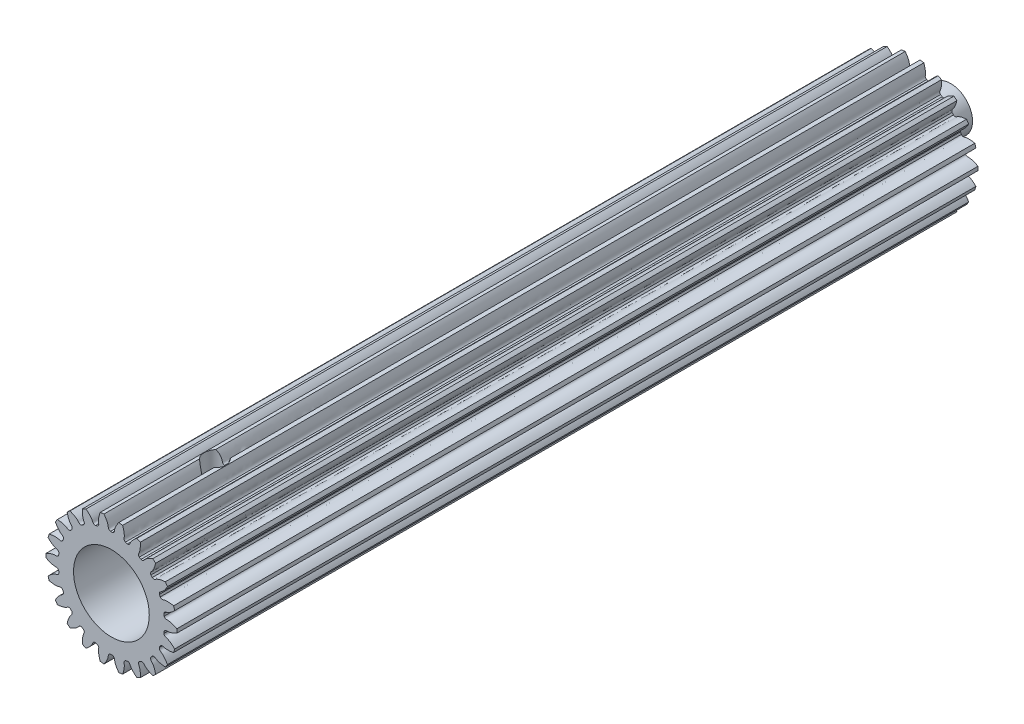
SolidWorks part; units mm, degrees
ref_plane "前视基准面" through (0, 0, 0) normal (0, 0, 1) x (1, 0, 0)
ref_plane "上视基准面" through (0, 0, 0) normal (0, 1, 0) x (1, 0, 0)
ref_plane "右视基准面" through (0, 0, 0) normal (1, 0, 0) x (0, 0, -1)
sketch "草图1" plane through (0, 0, 0) normal (0, 0, 1) x (1, 0, 0)
  circle A0 centre (0, 0) radius 12
extrude "凸台-拉伸1" add sketch "草图1" along normal blind 30
ref_axis "基准轴1" through (0, 0, -1.5) along (0, 0, 1)
sketch "草图2" plane through (0, 0, 0) normal (0, 0, 1) x (1, 0, 0)
  line L0 (0, 0) -> (0, 12) construction
  circle A0 centre (0, 0) radius 12 construction
  arc A1 (0.1857, 9.7482) -> (-0.1857, 9.7482) centre (0, 0) ccw
  arc A2 (3.0856, 13.5599) -> (-3.0856, 13.5599) centre (0, 0) ccw
  spline S0 degree 3 poles (0.1857, 9.7482) (0.5882, 9.8762) (0.5483, 10.1518) (0.5996, 10.4216) (0.606, 10.4519) (0.6139, 10.4862) (0.6235, 10.5243) (0.6349, 10.5661) (0.6484, 10.6117) (0.664, 10.661) (0.6819, 10.7139) (0.7023, 10.7703) (0.7253, 10.8301) (0.7511, 10.8933) (0.7797, 10.9597) (0.8114, 11.0293) (0.8462, 11.1021) (0.8843, 11.1778) (0.9259, 11.2563) (0.9711, 11.3377) (1.0199, 11.4217) (1.0726, 11.5082) (1.1292, 11.5972) (1.1899, 11.6884) (1.2547, 11.7818) (1.3238, 11.8773) (1.3973, 11.9746) (1.4753, 12.0737) (1.5579, 12.1744) (1.6452, 12.2766) (1.7372, 12.3802) (1.8341, 12.4849) (1.9359, 12.5906) (2.0428, 12.6972) (2.1547, 12.8044) (2.2718, 12.9123) (2.3942, 13.0205) (2.5218, 13.1289) (2.6548, 13.2373) (2.8415, 13.3834) (2.9864, 13.49) (3.0856, 13.5599) knots 0 0 0 0 0.157021 0.162531 0.168888 0.176093 0.184146 0.193046 0.202794 0.213389 0.224833 0.237123 0.250262 0.264248 0.279082 0.294763 0.311292 0.328669 0.346893 0.365965 0.385884 0.406652 0.428266 0.450729 0.474039 0.498197 0.523202 0.549055 0.575756 0.603304 0.6317 0.660944 0.691035 0.721974 0.75376 0.786395 0.819876 0.854206 0.889383 0.925408 1 1 1 1
  spline S1 degree 3 poles (-0.1857, 9.7482) (-0.5882, 9.8762) (-0.5483, 10.1518) (-0.5996, 10.4216) (-0.606, 10.4519) (-0.6139, 10.4862) (-0.6235, 10.5243) (-0.6349, 10.5661) (-0.6484, 10.6117) (-0.664, 10.661) (-0.6819, 10.7139) (-0.7023, 10.7703) (-0.7253, 10.8301) (-0.7511, 10.8933) (-0.7797, 10.9597) (-0.8114, 11.0293) (-0.8462, 11.1021) (-0.8843, 11.1778) (-0.9259, 11.2563) (-0.9711, 11.3377) (-1.0199, 11.4217) (-1.0726, 11.5082) (-1.1292, 11.5972) (-1.1899, 11.6884) (-1.2547, 11.7818) (-1.3238, 11.8773) (-1.3973, 11.9746) (-1.4753, 12.0737) (-1.5579, 12.1744) (-1.6452, 12.2766) (-1.7372, 12.3802) (-1.8341, 12.4849) (-1.9359, 12.5906) (-2.0428, 12.6972) (-2.1547, 12.8044) (-2.2718, 12.9123) (-2.3942, 13.0205) (-2.5218, 13.1289) (-2.6548, 13.2373) (-2.8415, 13.3834) (-2.9864, 13.49) (-3.0856, 13.5599) knots 0 0 0 0 0.157021 0.162531 0.168888 0.176093 0.184146 0.193046 0.202794 0.213389 0.224833 0.237123 0.250262 0.264248 0.279082 0.294763 0.311292 0.328669 0.346893 0.365965 0.385884 0.406652 0.428266 0.450729 0.474039 0.498197 0.523202 0.549055 0.575756 0.603304 0.6317 0.660944 0.691035 0.721974 0.75376 0.786395 0.819876 0.854206 0.889383 0.925408 1 1 1 1
extrude "切除-拉伸1" cut sketch "草图2" along normal through all
pattern_circular "阵列(圆周)1" count 22 every 16.364 about axis through (0, 0, -1.5) along (0, 0, 1) of "切除-拉伸1"
sketch "草图3" plane through (0, 0, 0) normal (0, 0, 1) x (1, 0, 0)
  circle A0 centre (0, 0) radius 11 construction
  dimension "Dn" = 22
sketch "草图4" plane through (0, 0, 0) normal (0, 0, -1) x (-1, 0, 0)
  arc A45 (2.9245, 9.3011) -> (2.5682, 9.4057) centre (0, 0) ccw
  arc A46 (2.0557, 11.8226) -> (1.3584, 11.9229) centre (0, 0) ccw
  arc A47 (0.1857, 9.7482) -> (-0.1857, 9.7482) centre (0, 0) ccw
  arc A48 (-1.3584, 11.9229) -> (-2.0557, 11.8226) centre (0, 0) ccw
  arc A49 (-2.5682, 9.4057) -> (-2.9245, 9.3011) centre (0, 0) ccw
  arc A50 (-4.6624, 11.0572) -> (-5.3032, 10.7646) centre (0, 0) ccw
  arc A51 (-5.1141, 8.3011) -> (-5.4265, 8.1004) centre (0, 0) ccw
  arc A52 (-7.5887, 9.2958) -> (-8.1211, 8.8344) centre (0, 0) ccw
  arc A53 (-7.2456, 6.5241) -> (-7.4888, 6.2434) centre (0, 0) ccw
  arc A54 (-9.9003, 6.7812) -> (-10.2811, 6.1886) centre (0, 0) ccw
  arc A55 (-8.7902, 4.2184) -> (-8.9444, 3.8807) centre (0, 0) ccw
  arc A56 (-11.4097, 3.7173) -> (-11.6082, 3.0414) centre (0, 0) ccw
  arc A57 (-9.6226, 1.5711) -> (-9.6754, 1.2035) centre (0, 0) ccw
  arc A58 (-11.9948, 0.3522) -> (-11.9948, -0.3522) centre (0, 0) ccw
  arc A59 (-9.6754, -1.2035) -> (-9.6226, -1.5711) centre (0, 0) ccw
  arc A60 (-11.6082, -3.0414) -> (-11.4097, -3.7173) centre (0, 0) ccw
  arc A61 (-8.9444, -3.8807) -> (-8.7902, -4.2184) centre (0, 0) ccw
  arc A62 (-10.2811, -6.1886) -> (-9.9003, -6.7812) centre (0, 0) ccw
  arc A63 (-7.4888, -6.2434) -> (-7.2456, -6.5241) centre (0, 0) ccw
  arc A64 (-8.1211, -8.8344) -> (-7.5887, -9.2958) centre (0, 0) ccw
  arc A65 (-5.4265, -8.1004) -> (-5.1141, -8.3011) centre (0, 0) ccw
  arc A66 (-5.3032, -10.7646) -> (-4.6624, -11.0572) centre (0, 0) ccw
  arc A67 (-2.9245, -9.3011) -> (-2.5682, -9.4057) centre (0, 0) ccw
  arc A68 (-2.0557, -11.8226) -> (-1.3584, -11.9229) centre (0, 0) ccw
  arc A69 (-0.1857, -9.7482) -> (0.1857, -9.7482) centre (0, 0) ccw
  arc A70 (1.3584, -11.9229) -> (2.0557, -11.8226) centre (0, 0) ccw
  arc A71 (2.5682, -9.4057) -> (2.9245, -9.3011) centre (0, 0) ccw
  arc A72 (4.6624, -11.0572) -> (5.3032, -10.7646) centre (0, 0) ccw
  arc A73 (5.1141, -8.3011) -> (5.4265, -8.1004) centre (0, 0) ccw
  arc A74 (7.5887, -9.2958) -> (8.1211, -8.8344) centre (0, 0) ccw
  arc A75 (7.2456, -6.5241) -> (7.4888, -6.2434) centre (0, 0) ccw
  arc A76 (9.9003, -6.7812) -> (10.2811, -6.1886) centre (0, 0) ccw
  arc A77 (8.7902, -4.2184) -> (8.9444, -3.8807) centre (0, 0) ccw
  arc A78 (11.4097, -3.7173) -> (11.6082, -3.0414) centre (0, 0) ccw
  arc A79 (9.6226, -1.5711) -> (9.6754, -1.2035) centre (0, 0) ccw
  arc A80 (11.9948, -0.3522) -> (11.9948, 0.3522) centre (0, 0) ccw
  arc A81 (9.6754, 1.2035) -> (9.6226, 1.5711) centre (0, 0) ccw
  arc A82 (11.6082, 3.0414) -> (11.4097, 3.7173) centre (0, 0) ccw
  arc A83 (8.9444, 3.8807) -> (8.7902, 4.2184) centre (0, 0) ccw
  arc A84 (10.2811, 6.1886) -> (9.9003, 6.7812) centre (0, 0) ccw
  arc A85 (7.4888, 6.2434) -> (7.2456, 6.5241) centre (0, 0) ccw
  arc A86 (8.1211, 8.8344) -> (7.5887, 9.2958) centre (0, 0) ccw
  arc A87 (5.4265, 8.1004) -> (5.1141, 8.3011) centre (0, 0) ccw
  arc A88 (5.3032, 10.7646) -> (4.6624, 11.0572) centre (0, 0) ccw
  arc A89 (2.9245, 9.3011) -> (2.5682, 9.4057) centre (0, 0) ccw
  arc A90 (2.0557, 11.8226) -> (1.3584, 11.9229) centre (0, 0) ccw
  arc A91 (0.1857, 9.7482) -> (-0.1857, 9.7482) centre (0, 0) ccw
  arc A92 (-1.3584, 11.9229) -> (-2.0557, 11.8226) centre (0, 0) ccw
  arc A93 (-2.5682, 9.4057) -> (-2.9245, 9.3011) centre (0, 0) ccw
  arc A94 (-4.6624, 11.0572) -> (-5.3032, 10.7646) centre (0, 0) ccw
  arc A95 (-5.1141, 8.3011) -> (-5.4265, 8.1004) centre (0, 0) ccw
  arc A96 (-7.5887, 9.2958) -> (-8.1211, 8.8344) centre (0, 0) ccw
  arc A97 (-7.2456, 6.5241) -> (-7.4888, 6.2434) centre (0, 0) ccw
  arc A98 (-9.9003, 6.7812) -> (-10.2811, 6.1886) centre (0, 0) ccw
  arc A99 (-8.7902, 4.2184) -> (-8.9444, 3.8807) centre (0, 0) ccw
  arc A100 (-11.4097, 3.7173) -> (-11.6082, 3.0414) centre (0, 0) ccw
  arc A101 (-9.6226, 1.5711) -> (-9.6754, 1.2035) centre (0, 0) ccw
  arc A102 (-11.9948, 0.3522) -> (-11.9948, -0.3522) centre (0, 0) ccw
  arc A103 (-9.6754, -1.2035) -> (-9.6226, -1.5711) centre (0, 0) ccw
  arc A104 (-11.6082, -3.0414) -> (-11.4097, -3.7173) centre (0, 0) ccw
  arc A105 (-8.9444, -3.8807) -> (-8.7902, -4.2184) centre (0, 0) ccw
  arc A106 (-10.2811, -6.1886) -> (-9.9003, -6.7812) centre (0, 0) ccw
  arc A107 (-7.4888, -6.2434) -> (-7.2456, -6.5241) centre (0, 0) ccw
  arc A108 (-8.1211, -8.8344) -> (-7.5887, -9.2958) centre (0, 0) ccw
  arc A109 (-5.4265, -8.1004) -> (-5.1141, -8.3011) centre (0, 0) ccw
  arc A110 (-5.3032, -10.7646) -> (-4.6624, -11.0572) centre (0, 0) ccw
  arc A111 (-2.9245, -9.3011) -> (-2.5682, -9.4057) centre (0, 0) ccw
  arc A112 (-2.0557, -11.8226) -> (-1.3584, -11.9229) centre (0, 0) ccw
  arc A113 (-0.1857, -9.7482) -> (0.1857, -9.7482) centre (0, 0) ccw
  arc A114 (1.3584, -11.9229) -> (2.0557, -11.8226) centre (0, 0) ccw
  arc A115 (2.5682, -9.4057) -> (2.9245, -9.3011) centre (0, 0) ccw
  arc A116 (4.6624, -11.0572) -> (5.3032, -10.7646) centre (0, 0) ccw
  arc A117 (5.1141, -8.3011) -> (5.4265, -8.1004) centre (0, 0) ccw
  arc A118 (7.5887, -9.2958) -> (8.1211, -8.8344) centre (0, 0) ccw
  arc A119 (7.2456, -6.5241) -> (7.4888, -6.2434) centre (0, 0) ccw
  arc A120 (9.9003, -6.7812) -> (10.2811, -6.1886) centre (0, 0) ccw
  arc A121 (8.7902, -4.2184) -> (8.9444, -3.8807) centre (0, 0) ccw
  arc A122 (11.4097, -3.7173) -> (11.6082, -3.0414) centre (0, 0) ccw
  arc A123 (9.6226, -1.5711) -> (9.6754, -1.2035) centre (0, 0) ccw
  arc A124 (11.9948, -0.3522) -> (11.9948, 0.3522) centre (0, 0) ccw
  arc A125 (9.6754, 1.2035) -> (9.6226, 1.5711) centre (0, 0) ccw
  arc A126 (11.6082, 3.0414) -> (11.4097, 3.7173) centre (0, 0) ccw
  arc A127 (8.9444, 3.8807) -> (8.7902, 4.2184) centre (0, 0) ccw
  arc A128 (10.2811, 6.1886) -> (9.9003, 6.7812) centre (0, 0) ccw
  arc A129 (7.4888, 6.2434) -> (7.2456, 6.5241) centre (0, 0) ccw
  arc A130 (8.1211, 8.8344) -> (7.5887, 9.2958) centre (0, 0) ccw
  arc A131 (5.4265, 8.1004) -> (5.1141, 8.3011) centre (0, 0) ccw
  arc A132 (5.3032, 10.7646) -> (4.6624, 11.0572) centre (0, 0) ccw
  spline S44 degree 3 poles (-3755.952, 1373.0737) (154.5775, -91.5166) (23.7539, 27.4151) (4.2738, 10.7434) (4.1283, 10.6084) (3.9999, 10.4794) (3.888, 10.3576) (3.7917, 10.2441) (3.7102, 10.1398) (3.6518, 10.0587) (3.6037, 9.9872) (3.5713, 9.9359) (3.5381, 9.8795) (3.5167, 9.8409) (1.2241, 5.3639) (28.0313, -13.6031) (-3366.6388, 2164.2652) knots -15.132265 -15.132265 -15.132265 -15.132265 0.549271 0.593348 0.634035 0.671331 0.705237 0.735752 0.762877 0.786611 0.797206 0.815854 0.823907 0.837469 0.842979 3.91725 3.91725 3.91725 3.91725 only from (4.6624, 11.0572) to (2.9245, 9.3011)
  spline S45 degree 3 poles (4001.8856, 0.5536) (-30.9337, 3.7113) (1.8702, 5.1744) (2.3619, 10.18) (2.3658, 10.2385) (2.3681, 10.3211) (2.3668, 10.4204) (2.3608, 10.536) (2.3486, 10.6678) (2.329, 10.8154) (2.3007, 10.9784) (2.2624, 11.1562) (2.213, 11.3485) (2.1511, 11.5544) (-6.7232, 37.3225) (-188.8794, -0.555) (3905.063, -861.7664) knots -2.917148 -2.917148 -2.917148 -2.917148 0.157021 0.162531 0.176093 0.193046 0.213389 0.237123 0.264248 0.294763 0.328669 0.365965 0.406652 0.450729 0.498197 17.164861 17.164861 17.164861 17.164861 only from (2.5682, 9.4057) to (2.0557, 11.8226)
  spline S46 degree 3 poles (-3990.6492, 259.2806) (174.0992, -44.26) (15.0679, 32.9969) (1.0739, 11.5123) (0.9723, 11.3417) (0.8855, 11.1818) (0.8124, 11.0334) (0.752, 10.8973) (0.7032, 10.7743) (0.6701, 10.6801) (0.644, 10.5979) (0.6274, 10.5396) (0.6113, 10.4761) (0.6018, 10.4331) (-0.3367, 5.4915) (30.7283, -5.1547) (-3840.0103, 1128.1054) knots -15.132265 -15.132265 -15.132265 -15.132265 0.549271 0.593348 0.634035 0.671331 0.705237 0.735752 0.762877 0.786611 0.797206 0.815854 0.823907 0.837469 0.842979 3.91725 3.91725 3.91725 3.91725 only from (1.3584, 11.9229) to (0.1857, 9.7482)
  spline S47 degree 3 poles (3839.6251, 1127.9927) (-30.7262, -5.154) (0.3366, 5.4917) (-0.6018, 10.4331) (-0.6145, 10.4903) (-0.6356, 10.5702) (-0.6648, 10.6651) (-0.7032, 10.7743) (-0.752, 10.8973) (-0.8124, 11.0334) (-0.8855, 11.1818) (-0.9723, 11.3417) (-1.0739, 11.5123) (-1.1913, 11.6924) (-16.9659, 33.9165) (-181.0721, -53.746) (3989.6681, 273.3246) knots -2.917148 -2.917148 -2.917148 -2.917148 0.157021 0.162531 0.176093 0.193046 0.213389 0.237123 0.264248 0.294763 0.328669 0.365965 0.406652 0.450729 0.498197 17.164861 17.164861 17.164861 17.164861 only from (-0.1857, 9.7482) to (-1.3584, 11.9229)
  spline S48 degree 3 poles (-3902.0476, -875.5179) (179.5164, 6.5822) (5.1613, 35.9054) (-2.213, 11.3485) (-2.2624, 11.1562) (-2.3007, 10.9784) (-2.329, 10.8154) (-2.3486, 10.6678) (-2.3608, 10.536) (-2.366, 10.4362) (-2.3678, 10.3501) (-2.3674, 10.2894) (-2.3649, 10.224) (-2.3619, 10.18) (-1.8702, 5.1742) (30.9358, 3.7112) (-4002.2869, 0.5533) knots -15.132265 -15.132265 -15.132265 -15.132265 0.549271 0.593348 0.634035 0.671331 0.705237 0.735752 0.762877 0.786611 0.797206 0.815854 0.823907 0.837469 0.842979 3.91725 3.91725 3.91725 3.91725 only from (-2.0557, 11.8226) to (-2.5682, 9.4057)
  spline S49 degree 3 poles (3366.3011, 2164.0485) (-28.0295, -13.6018) (-1.2242, 5.3641) (-3.5167, 9.8409) (-3.5451, 9.8922) (-3.5879, 9.963) (-3.6426, 10.0458) (-3.7102, 10.1398) (-3.7917, 10.2441) (-3.888, 10.3576) (-3.9999, 10.4794) (-4.1283, 10.6084) (-4.2738, 10.7434) (-4.4372, 10.8832) (-25.834, 27.7628) (-158.5954, -102.5828) (3751.0541, 1386.2724) knots -2.917148 -2.917148 -2.917148 -2.917148 0.157021 0.162531 0.176093 0.193046 0.213389 0.237123 0.264248 0.294763 0.328669 0.365965 0.406652 0.450729 0.498197 17.164861 17.164861 17.164861 17.164861 only from (-2.9245, 9.3011) to (-4.6624, 11.0572)
  spline S50 degree 3 poles (-3497.3254, -1939.3871) (170.3903, 56.8912) (-5.1635, 35.9051) (-5.3206, 10.2653) (-5.3138, 10.0669) (-5.3004, 9.8855) (-5.2817, 9.7211) (-5.2589, 9.574) (-5.2335, 9.4441) (-5.2104, 9.3469) (-5.1879, 9.2637) (-5.1704, 9.2057) (-5.1495, 9.1436) (-5.1343, 9.1022) (-3.2522, 4.4377) (28.6371, 12.2765) (-3840.322, -1127.0436) knots -15.132265 -15.132265 -15.132265 -15.132265 0.549271 0.593348 0.634035 0.671331 0.705237 0.735752 0.762877 0.786611 0.797206 0.815854 0.823907 0.837469 0.842979 3.91725 3.91725 3.91725 3.91725 only from (-5.3032, 10.7646) to (-5.1141, 8.3011)
  spline S51 degree 3 poles (2620.2593, 3024.7859) (-23.0621, -20.9477) (-2.6858, 4.8019) (-6.1468, 8.4515) (-6.1884, 8.4928) (-6.2494, 8.5486) (-6.3253, 8.6126) (-6.4166, 8.6838) (-6.5242, 8.7609) (-6.6486, 8.8427) (-6.7903, 8.928) (-6.9498, 9.0156) (-7.1274, 9.1041) (-7.3236, 9.1923) (-32.6092, 19.3599) (-123.2703, -143.109) (3208.552, 2386.9127) knots -2.917148 -2.917148 -2.917148 -2.917148 0.157021 0.162531 0.176093 0.193046 0.213389 0.237123 0.264248 0.294763 0.328669 0.365965 0.406652 0.450729 0.498197 17.164861 17.164861 17.164861 17.164861 only from (-5.4265, 8.1004) to (-7.5887, 9.2958)
  spline S52 degree 3 poles (-2809.2707, -2846.1387) (147.4602, 102.5913) (-15.07, 32.9959) (-7.9971, 8.3505) (-7.9348, 8.1621) (-7.8708, 7.9917) (-7.8065, 7.8393) (-7.7432, 7.7046) (-7.6822, 7.5871) (-7.6327, 7.5003) (-7.5876, 7.4269) (-7.5545, 7.3761) (-7.517, 7.3224) (-7.4907, 7.287) (-4.3707, 3.3417) (24.0184, 19.8472) (-3367.2371, -2163.3342) knots -15.132265 -15.132265 -15.132265 -15.132265 0.549271 0.593348 0.634035 0.671331 0.705237 0.735752 0.762877 0.786611 0.797206 0.815854 0.823907 0.837469 0.842979 3.91725 3.91725 3.91725 3.91725 only from (-8.1211, 8.8344) to (-7.2456, 6.5241)
  spline S53 degree 3 poles (1661.9397, 3640.4732) (-16.2262, -26.5965) (-3.9299, 3.8507) (-8.2789, 6.3774) (-8.3304, 6.4053) (-8.4047, 6.4416) (-8.4955, 6.4817) (-8.6032, 6.5243) (-8.7281, 6.5679) (-8.8705, 6.6114) (-9.0305, 6.6533) (-9.2082, 6.6924) (-9.4036, 6.7273) (-9.6167, 6.7566) (-36.7427, 9.3886) (-77.9585, -172.0413) (2406.1121, 3194.1795) knots -2.917148 -2.917148 -2.917148 -2.917148 0.157021 0.162531 0.176093 0.193046 0.213389 0.237123 0.264248 0.294763 0.328669 0.365965 0.406652 0.450729 0.498197 17.164861 17.164861 17.164861 17.164861 only from (-7.4888, 6.2434) to (-9.9003, 6.7812)
  spline S54 degree 3 poles (-1893.6255, -3522.3131) (112.5837, 139.9799) (-23.7556, 27.4137) (-10.0258, 5.7592) (-9.9129, 5.596) (-9.8035, 5.4506) (-9.6989, 5.3224) (-9.6002, 5.211) (-9.5086, 5.1155) (-9.4366, 5.0462) (-9.3727, 4.9884) (-9.3266, 4.949) (-9.2755, 4.908) (-9.2403, 4.8814) (-5.1351, 1.975) (17.4539, 25.8101) (-2621.3587, -3024.3643) knots -15.132265 -15.132265 -15.132265 -15.132265 0.549271 0.593348 0.634035 0.671331 0.705237 0.735752 0.762877 0.786611 0.797206 0.815854 0.823907 0.837469 0.842979 3.91725 3.91725 3.91725 3.91725 only from (-10.2811, 6.1886) to (-8.7902, 4.2184)
  spline S55 degree 3 poles (568.9797, 3961.231) (-8.0759, -30.0906) (-4.8556, 2.5876) (-9.7402, 3.7867) (-9.7976, 3.7989) (-9.8791, 3.8128) (-9.9775, 3.8257) (-10.0928, 3.8362) (-10.225, 3.8429) (-10.3738, 3.8445) (-10.5392, 3.8396) (-10.7207, 3.8271) (-10.918, 3.8055) (-11.1307, 3.7736) (-37.8994, -1.3433) (-26.331, -187.0359) (1408.7433, 3742.6729) knots -2.917148 -2.917148 -2.917148 -2.917148 0.157021 0.162531 0.176093 0.193046 0.213389 0.237123 0.264248 0.294763 0.328669 0.365965 0.406652 0.450729 0.498197 17.164861 17.164861 17.164861 17.164861 only from (-8.9444, 3.8807) to (-11.4097, 3.7173)
  spline S56 degree 3 poles (-824.5701, -3913.1306) (68.5864, 166.0283) (-30.5166, 19.6105) (-11.2422, 2.7013) (-11.0879, 2.5765) (-10.942, 2.4678) (-10.8055, 2.3743) (-10.6794, 2.2952) (-10.5646, 2.2294) (-10.476, 2.1832) (-10.3984, 2.1457) (-10.3431, 2.1209) (-10.2825, 2.096) (-10.2412, 2.0804) (-5.4835, 0.4483) (9.4754, 29.6819) (-1663.1134, -3640.3784) knots -15.132265 -15.132265 -15.132265 -15.132265 0.549271 0.593348 0.634035 0.671331 0.705237 0.735752 0.762877 0.786611 0.797206 0.815854 0.823907 0.837469 0.842979 3.91725 3.91725 3.91725 3.91725 only from (-11.6082, 3.0414) to (-9.6226, 1.5711)
  spline S57 degree 3 poles (-570.0757, 3961.0734) (0.7288, -31.147) (-5.3879, 1.1148) (-10.4125, 0.8891) (-10.4709, 0.8847) (-10.5531, 0.8751) (-10.6512, 0.8598) (-10.7647, 0.8373) (-10.8934, 0.8065) (-11.0367, 0.7661) (-11.194, 0.7149) (-11.3647, 0.6517) (-11.5479, 0.5754) (-11.743, 0.4849) (-35.9858, -11.9664) (27.4296, -186.8779) (297.2464, 3987.9572) knots -2.917148 -2.917148 -2.917148 -2.917148 0.157021 0.162531 0.176093 0.193046 0.213389 0.237123 0.264248 0.294763 0.328669 0.365965 0.406652 0.450729 0.498197 17.164861 17.164861 17.164861 17.164861 only from (-9.6754, 1.2035) to (-11.9948, 0.3522)
  spline S58 degree 3 poles (311.2871, -3986.9296) (19.0326, 178.626) (-34.8054, 10.2186) (-11.5479, -0.5754) (-11.3647, -0.6517) (-11.194, -0.7149) (-11.0367, -0.7661) (-10.8934, -0.8065) (-10.7647, -0.8373) (-10.6667, -0.8567) (-10.5817, -0.8708) (-10.5216, -0.879) (-10.4565, -0.8858) (-10.4125, -0.8891) (-5.3877, -1.1148) (0.7292, 31.1491) (-570.1325, -3961.4706) knots -15.132265 -15.132265 -15.132265 -15.132265 0.549271 0.593348 0.634035 0.671331 0.705237 0.735752 0.762877 0.786611 0.797206 0.815854 0.823907 0.837469 0.842979 3.91725 3.91725 3.91725 3.91725 only from (-11.9948, -0.3522) to (-9.6754, -1.2035)
  spline S59 degree 3 poles (-1662.947, 3640.0132) (9.4744, -29.68) (-5.4837, -0.4483) (-10.2412, -2.0804) (-10.296, -2.1012) (-10.3722, -2.1335) (-10.4619, -2.1758) (-10.5646, -2.2294) (-10.6794, -2.2952) (-10.8055, -2.3743) (-10.942, -2.4678) (-11.0879, -2.5765) (-11.2422, -2.7014) (-11.4039, -2.8432) (-31.1568, -21.62) (78.9681, -171.5802) (-838.3315, 3910.1609) knots -2.917148 -2.917148 -2.917148 -2.917148 0.157021 0.162531 0.176093 0.193046 0.213389 0.237123 0.264248 0.294763 0.328669 0.365965 0.406652 0.450729 0.498197 17.164861 17.164861 17.164861 17.164861 only from (-9.6226, -1.5711) to (-11.6082, -3.0414)
  spline S60 degree 3 poles (1421.9256, -3737.7312) (-32.0631, 176.7525) (-36.2745, -0.0011) (-10.918, -3.8055) (-10.7207, -3.8271) (-10.5392, -3.8396) (-10.3738, -3.8445) (-10.225, -3.8429) (-10.0928, -3.8362) (-9.9933, -3.8272) (-9.9078, -3.8167) (-9.8478, -3.8076) (-9.7834, -3.7958) (-9.7402, -3.7867) (-4.8554, -2.5875) (-8.0761, 30.0928) (569.0371, -3961.6281) knots -15.132265 -15.132265 -15.132265 -15.132265 0.549271 0.593348 0.634035 0.671331 0.705237 0.735752 0.762877 0.786611 0.797206 0.815854 0.823907 0.837469 0.842979 3.91725 3.91725 3.91725 3.91725 only from (-11.4097, -3.7173) to (-8.9444, -3.8807)
  spline S61 degree 3 poles (-2621.0962, 3024.0608) (17.4524, -25.8085) (-5.1353, -1.9751) (-9.2403, -4.8814) (-9.287, -4.9168) (-9.351, -4.9692) (-9.4251, -5.0352) (-9.5086, -5.1155) (-9.6002, -5.211) (-9.6989, -5.3224) (-9.8035, -5.4506) (-9.9129, -5.596) (-10.0258, -5.7592) (-10.1409, -5.9408) (-23.8037, -29.5221) (124.1091, -142.3821) (-1905.9928, 3515.5866) knots -2.917148 -2.917148 -2.917148 -2.917148 0.157021 0.162531 0.176093 0.193046 0.213389 0.237123 0.264248 0.294763 0.328669 0.365965 0.406652 0.450729 0.498197 17.164861 17.164861 17.164861 17.164861 only from (-8.7902, -4.2184) to (-10.2811, -6.1886)
  spline S62 degree 3 poles (2417.3682, -3185.7241) (-80.5613, 160.5595) (-34.8048, -10.2208) (-9.4036, -6.7273) (-9.2082, -6.6924) (-9.0305, -6.6533) (-8.8705, -6.6114) (-8.7281, -6.5679) (-8.6032, -6.5243) (-8.5102, -6.4876) (-8.4311, -6.4535) (-8.3761, -6.4279) (-8.3177, -6.3984) (-8.2789, -6.3774) (-3.9297, -3.8506) (-16.227, 26.5985) (1662.1067, -3640.8381) knots -15.132265 -15.132265 -15.132265 -15.132265 0.549271 0.593348 0.634035 0.671331 0.705237 0.735752 0.762877 0.786611 0.797206 0.815854 0.823907 0.837469 0.842979 3.91725 3.91725 3.91725 3.91725 only from (-9.9003, -6.7812) to (-7.4888, -6.2434)
  spline S63 degree 3 poles (-3366.8997, 2163.1169) (24.0166, -19.8462) (-4.3708, -3.3419) (-7.4907, -7.287) (-7.5256, -7.3341) (-7.5722, -7.4024) (-7.6248, -7.4866) (-7.6822, -7.5871) (-7.7432, -7.7046) (-7.8065, -7.8393) (-7.8708, -7.9917) (-7.9348, -8.1621) (-7.9971, -8.3505) (-8.0564, -8.5572) (-14.5221, -35.0325) (159.1955, -101.6491) (-2819.2419, 2836.2005) knots -2.917148 -2.917148 -2.917148 -2.917148 0.157021 0.162531 0.176093 0.193046 0.213389 0.237123 0.264248 0.294763 0.328669 0.365965 0.406652 0.450729 0.498197 17.164861 17.164861 17.164861 17.164861 only from (-7.2456, -6.5241) to (-8.1211, -8.8344)
  spline S64 degree 3 poles (3216.97, -2375.6286) (-122.5328, 131.359) (-30.5154, -19.6124) (-7.1274, -9.1041) (-6.9498, -9.0156) (-6.7903, -8.928) (-6.6486, -8.8427) (-6.5242, -8.7609) (-6.4166, -8.6838) (-6.3378, -8.6224) (-6.2715, -8.5674) (-6.2259, -8.5273) (-6.1781, -8.4826) (-6.1468, -8.4515) (-2.6857, -4.8018) (-23.0634, 20.9494) (2620.5224, -3025.089) knots -15.132265 -15.132265 -15.132265 -15.132265 0.549271 0.593348 0.634035 0.671331 0.705237 0.735752 0.762877 0.786611 0.797206 0.815854 0.823907 0.837469 0.842979 3.91725 3.91725 3.91725 3.91725 only from (-7.5887, -9.2958) to (-5.4265, -8.1004)
  spline S65 degree 3 poles (-3839.9371, 1126.9302) (28.635, -12.276) (-3.2522, -4.4379) (-5.1343, -9.1022) (-5.1545, -9.1572) (-5.18, -9.2359) (-5.2067, -9.3315) (-5.2335, -9.4441) (-5.2589, -9.574) (-5.2817, -9.7211) (-5.3004, -9.8855) (-5.3138, -10.0669) (-5.3206, -10.2653) (-5.3192, -10.4804) (-4.0641, -37.7048) (181.3848, -52.681) (-3504.0928, 1927.0422) knots -2.917148 -2.917148 -2.917148 -2.917148 0.157021 0.162531 0.176093 0.193046 0.213389 0.237123 0.264248 0.294763 0.328669 0.365965 0.406652 0.450729 0.498197 17.164861 17.164861 17.164861 17.164861 only from (-5.1141, -8.3011) to (-5.3032, -10.7646)
  spline S66 degree 3 poles (3755.952, -1373.0737) (-154.5775, 91.5166) (-23.7539, -27.4151) (-4.2738, -10.7434) (-4.1283, -10.6084) (-3.9999, -10.4794) (-3.888, -10.3576) (-3.7917, -10.2441) (-3.7102, -10.1398) (-3.6518, -10.0587) (-3.6037, -9.9872) (-3.5713, -9.9359) (-3.5381, -9.8795) (-3.5167, -9.8409) (-1.2241, -5.3639) (-28.0313, 13.6031) (3366.6388, -2164.2652) knots -15.132265 -15.132265 -15.132265 -15.132265 0.549271 0.593348 0.634035 0.671331 0.705237 0.735752 0.762877 0.786611 0.797206 0.815854 0.823907 0.837469 0.842979 3.91725 3.91725 3.91725 3.91725 only from (-4.6624, -11.0572) to (-2.9245, -9.3011)
  spline S67 degree 3 poles (-4001.8856, -0.5536) (30.9337, -3.7113) (-1.8702, -5.1744) (-2.3619, -10.18) (-2.3658, -10.2385) (-2.3681, -10.3211) (-2.3668, -10.4204) (-2.3608, -10.536) (-2.3486, -10.6678) (-2.329, -10.8154) (-2.3007, -10.9784) (-2.2624, -11.1562) (-2.213, -11.3485) (-2.1511, -11.5544) (6.7232, -37.3225) (188.8794, 0.555) (-3905.063, 861.7664) knots -2.917148 -2.917148 -2.917148 -2.917148 0.157021 0.162531 0.176093 0.193046 0.213389 0.237123 0.264248 0.294763 0.328669 0.365965 0.406652 0.450729 0.498197 17.164861 17.164861 17.164861 17.164861 only from (-2.5682, -9.4057) to (-2.0557, -11.8226)
  spline S68 degree 3 poles (3990.6492, -259.2806) (-174.0992, 44.26) (-15.0679, -32.9969) (-1.0739, -11.5123) (-0.9723, -11.3417) (-0.8855, -11.1818) (-0.8124, -11.0334) (-0.752, -10.8973) (-0.7032, -10.7743) (-0.6701, -10.6801) (-0.644, -10.5979) (-0.6274, -10.5396) (-0.6113, -10.4761) (-0.6018, -10.4331) (0.3367, -5.4915) (-30.7283, 5.1547) (3840.0103, -1128.1054) knots -15.132265 -15.132265 -15.132265 -15.132265 0.549271 0.593348 0.634035 0.671331 0.705237 0.735752 0.762877 0.786611 0.797206 0.815854 0.823907 0.837469 0.842979 3.91725 3.91725 3.91725 3.91725 only from (-1.3584, -11.9229) to (-0.1857, -9.7482)
  spline S69 degree 3 poles (-3839.6251, -1127.9927) (30.7262, 5.154) (-0.3366, -5.4917) (0.6018, -10.4331) (0.6145, -10.4903) (0.6356, -10.5702) (0.6648, -10.6651) (0.7032, -10.7743) (0.752, -10.8973) (0.8124, -11.0334) (0.8855, -11.1818) (0.9723, -11.3417) (1.0739, -11.5123) (1.1913, -11.6924) (16.9659, -33.9165) (181.0721, 53.746) (-3989.6681, -273.3246) knots -2.917148 -2.917148 -2.917148 -2.917148 0.157021 0.162531 0.176093 0.193046 0.213389 0.237123 0.264248 0.294763 0.328669 0.365965 0.406652 0.450729 0.498197 17.164861 17.164861 17.164861 17.164861 only from (0.1857, -9.7482) to (1.3584, -11.9229)
  spline S70 degree 3 poles (3902.0476, 875.5179) (-179.5164, -6.5822) (-5.1613, -35.9054) (2.213, -11.3485) (2.2624, -11.1562) (2.3007, -10.9784) (2.329, -10.8154) (2.3486, -10.6678) (2.3608, -10.536) (2.366, -10.4362) (2.3678, -10.3501) (2.3674, -10.2894) (2.3649, -10.224) (2.3619, -10.18) (1.8702, -5.1742) (-30.9358, -3.7112) (4002.2869, -0.5533) knots -15.132265 -15.132265 -15.132265 -15.132265 0.549271 0.593348 0.634035 0.671331 0.705237 0.735752 0.762877 0.786611 0.797206 0.815854 0.823907 0.837469 0.842979 3.91725 3.91725 3.91725 3.91725 only from (2.0557, -11.8226) to (2.5682, -9.4057)
  spline S71 degree 3 poles (-3366.3011, -2164.0485) (28.0295, 13.6018) (1.2242, -5.3641) (3.5167, -9.8409) (3.5451, -9.8922) (3.5879, -9.963) (3.6426, -10.0458) (3.7102, -10.1398) (3.7917, -10.2441) (3.888, -10.3576) (3.9999, -10.4794) (4.1283, -10.6084) (4.2738, -10.7434) (4.4372, -10.8832) (25.834, -27.7628) (158.5954, 102.5828) (-3751.0541, -1386.2724) knots -2.917148 -2.917148 -2.917148 -2.917148 0.157021 0.162531 0.176093 0.193046 0.213389 0.237123 0.264248 0.294763 0.328669 0.365965 0.406652 0.450729 0.498197 17.164861 17.164861 17.164861 17.164861 only from (2.9245, -9.3011) to (4.6624, -11.0572)
  spline S72 degree 3 poles (3497.3254, 1939.3871) (-170.3903, -56.8912) (5.1635, -35.9051) (5.3206, -10.2653) (5.3138, -10.0669) (5.3004, -9.8855) (5.2817, -9.7211) (5.2589, -9.574) (5.2335, -9.4441) (5.2104, -9.3469) (5.1879, -9.2637) (5.1704, -9.2057) (5.1495, -9.1436) (5.1343, -9.1022) (3.2522, -4.4377) (-28.6371, -12.2765) (3840.322, 1127.0436) knots -15.132265 -15.132265 -15.132265 -15.132265 0.549271 0.593348 0.634035 0.671331 0.705237 0.735752 0.762877 0.786611 0.797206 0.815854 0.823907 0.837469 0.842979 3.91725 3.91725 3.91725 3.91725 only from (5.3032, -10.7646) to (5.1141, -8.3011)
  spline S73 degree 3 poles (-2620.2593, -3024.7859) (23.0621, 20.9477) (2.6858, -4.8019) (6.1468, -8.4515) (6.1884, -8.4928) (6.2494, -8.5486) (6.3253, -8.6126) (6.4166, -8.6838) (6.5242, -8.7609) (6.6486, -8.8427) (6.7903, -8.928) (6.9498, -9.0156) (7.1274, -9.1041) (7.3236, -9.1923) (32.6092, -19.3599) (123.2703, 143.109) (-3208.552, -2386.9127) knots -2.917148 -2.917148 -2.917148 -2.917148 0.157021 0.162531 0.176093 0.193046 0.213389 0.237123 0.264248 0.294763 0.328669 0.365965 0.406652 0.450729 0.498197 17.164861 17.164861 17.164861 17.164861 only from (5.4265, -8.1004) to (7.5887, -9.2958)
  spline S74 degree 3 poles (2809.2707, 2846.1387) (-147.4602, -102.5913) (15.07, -32.9959) (7.9971, -8.3505) (7.9348, -8.1621) (7.8708, -7.9917) (7.8065, -7.8393) (7.7432, -7.7046) (7.6822, -7.5871) (7.6327, -7.5003) (7.5876, -7.4269) (7.5545, -7.3761) (7.517, -7.3224) (7.4907, -7.287) (4.3707, -3.3417) (-24.0184, -19.8472) (3367.2371, 2163.3342) knots -15.132265 -15.132265 -15.132265 -15.132265 0.549271 0.593348 0.634035 0.671331 0.705237 0.735752 0.762877 0.786611 0.797206 0.815854 0.823907 0.837469 0.842979 3.91725 3.91725 3.91725 3.91725 only from (8.1211, -8.8344) to (7.2456, -6.5241)
  spline S75 degree 3 poles (-1661.9397, -3640.4732) (16.2262, 26.5965) (3.9299, -3.8507) (8.2789, -6.3774) (8.3304, -6.4053) (8.4047, -6.4416) (8.4955, -6.4817) (8.6032, -6.5243) (8.7281, -6.5679) (8.8705, -6.6114) (9.0305, -6.6533) (9.2082, -6.6924) (9.4036, -6.7273) (9.6167, -6.7566) (36.7427, -9.3886) (77.9585, 172.0413) (-2406.1121, -3194.1795) knots -2.917148 -2.917148 -2.917148 -2.917148 0.157021 0.162531 0.176093 0.193046 0.213389 0.237123 0.264248 0.294763 0.328669 0.365965 0.406652 0.450729 0.498197 17.164861 17.164861 17.164861 17.164861 only from (7.4888, -6.2434) to (9.9003, -6.7812)
  spline S76 degree 3 poles (1893.6255, 3522.3131) (-112.5837, -139.9799) (23.7556, -27.4137) (10.0258, -5.7592) (9.9129, -5.596) (9.8035, -5.4506) (9.6989, -5.3224) (9.6002, -5.211) (9.5086, -5.1155) (9.4366, -5.0462) (9.3727, -4.9884) (9.3266, -4.949) (9.2755, -4.908) (9.2403, -4.8814) (5.1351, -1.975) (-17.4539, -25.8101) (2621.3587, 3024.3643) knots -15.132265 -15.132265 -15.132265 -15.132265 0.549271 0.593348 0.634035 0.671331 0.705237 0.735752 0.762877 0.786611 0.797206 0.815854 0.823907 0.837469 0.842979 3.91725 3.91725 3.91725 3.91725 only from (10.2811, -6.1886) to (8.7902, -4.2184)
  spline S77 degree 3 poles (-568.9797, -3961.231) (8.0759, 30.0906) (4.8556, -2.5876) (9.7402, -3.7867) (9.7976, -3.7989) (9.8791, -3.8128) (9.9775, -3.8257) (10.0928, -3.8362) (10.225, -3.8429) (10.3738, -3.8445) (10.5392, -3.8396) (10.7207, -3.8271) (10.918, -3.8055) (11.1307, -3.7736) (37.8994, 1.3433) (26.331, 187.0359) (-1408.7433, -3742.6729) knots -2.917148 -2.917148 -2.917148 -2.917148 0.157021 0.162531 0.176093 0.193046 0.213389 0.237123 0.264248 0.294763 0.328669 0.365965 0.406652 0.450729 0.498197 17.164861 17.164861 17.164861 17.164861 only from (8.9444, -3.8807) to (11.4097, -3.7173)
  spline S78 degree 3 poles (824.5701, 3913.1306) (-68.5864, -166.0283) (30.5166, -19.6105) (11.2422, -2.7013) (11.0879, -2.5765) (10.942, -2.4678) (10.8055, -2.3743) (10.6794, -2.2952) (10.5646, -2.2294) (10.476, -2.1832) (10.3984, -2.1457) (10.3431, -2.1209) (10.2825, -2.096) (10.2412, -2.0804) (5.4835, -0.4483) (-9.4754, -29.6819) (1663.1134, 3640.3784) knots -15.132265 -15.132265 -15.132265 -15.132265 0.549271 0.593348 0.634035 0.671331 0.705237 0.735752 0.762877 0.786611 0.797206 0.815854 0.823907 0.837469 0.842979 3.91725 3.91725 3.91725 3.91725 only from (11.6082, -3.0414) to (9.6226, -1.5711)
  spline S79 degree 3 poles (570.0757, -3961.0734) (-0.7288, 31.147) (5.3879, -1.1148) (10.4125, -0.8891) (10.4709, -0.8847) (10.5531, -0.8751) (10.6512, -0.8598) (10.7647, -0.8373) (10.8934, -0.8065) (11.0367, -0.7661) (11.194, -0.7149) (11.3647, -0.6517) (11.5479, -0.5754) (11.743, -0.4849) (35.9858, 11.9664) (-27.4296, 186.8779) (-297.2464, -3987.9572) knots -2.917148 -2.917148 -2.917148 -2.917148 0.157021 0.162531 0.176093 0.193046 0.213389 0.237123 0.264248 0.294763 0.328669 0.365965 0.406652 0.450729 0.498197 17.164861 17.164861 17.164861 17.164861 only from (9.6754, -1.2035) to (11.9948, -0.3522)
  spline S80 degree 3 poles (-311.2871, 3986.9296) (-19.0326, -178.626) (34.8054, -10.2186) (11.5479, 0.5754) (11.3647, 0.6517) (11.194, 0.7149) (11.0367, 0.7661) (10.8934, 0.8065) (10.7647, 0.8373) (10.6667, 0.8567) (10.5817, 0.8708) (10.5216, 0.879) (10.4565, 0.8858) (10.4125, 0.8891) (5.3877, 1.1148) (-0.7292, -31.1491) (570.1325, 3961.4706) knots -15.132265 -15.132265 -15.132265 -15.132265 0.549271 0.593348 0.634035 0.671331 0.705237 0.735752 0.762877 0.786611 0.797206 0.815854 0.823907 0.837469 0.842979 3.91725 3.91725 3.91725 3.91725 only from (11.9948, 0.3522) to (9.6754, 1.2035)
  spline S81 degree 3 poles (1662.947, -3640.0132) (-9.4744, 29.68) (5.4837, 0.4483) (10.2412, 2.0804) (10.296, 2.1012) (10.3722, 2.1335) (10.4619, 2.1758) (10.5646, 2.2294) (10.6794, 2.2952) (10.8055, 2.3743) (10.942, 2.4678) (11.0879, 2.5765) (11.2422, 2.7014) (11.4039, 2.8432) (31.1568, 21.62) (-78.9681, 171.5802) (838.3315, -3910.1609) knots -2.917148 -2.917148 -2.917148 -2.917148 0.157021 0.162531 0.176093 0.193046 0.213389 0.237123 0.264248 0.294763 0.328669 0.365965 0.406652 0.450729 0.498197 17.164861 17.164861 17.164861 17.164861 only from (9.6226, 1.5711) to (11.6082, 3.0414)
  spline S82 degree 3 poles (-1421.9256, 3737.7312) (32.0631, -176.7525) (36.2745, 0.0011) (10.918, 3.8055) (10.7207, 3.8271) (10.5392, 3.8396) (10.3738, 3.8445) (10.225, 3.8429) (10.0928, 3.8362) (9.9933, 3.8272) (9.9078, 3.8167) (9.8478, 3.8076) (9.7834, 3.7958) (9.7402, 3.7867) (4.8554, 2.5875) (8.0761, -30.0928) (-569.0371, 3961.6281) knots -15.132265 -15.132265 -15.132265 -15.132265 0.549271 0.593348 0.634035 0.671331 0.705237 0.735752 0.762877 0.786611 0.797206 0.815854 0.823907 0.837469 0.842979 3.91725 3.91725 3.91725 3.91725 only from (11.4097, 3.7173) to (8.9444, 3.8807)
  spline S83 degree 3 poles (2621.0962, -3024.0608) (-17.4524, 25.8085) (5.1353, 1.9751) (9.2403, 4.8814) (9.287, 4.9168) (9.351, 4.9692) (9.4251, 5.0352) (9.5086, 5.1155) (9.6002, 5.211) (9.6989, 5.3224) (9.8035, 5.4506) (9.9129, 5.596) (10.0258, 5.7592) (10.1409, 5.9408) (23.8037, 29.5221) (-124.1091, 142.3821) (1905.9928, -3515.5866) knots -2.917148 -2.917148 -2.917148 -2.917148 0.157021 0.162531 0.176093 0.193046 0.213389 0.237123 0.264248 0.294763 0.328669 0.365965 0.406652 0.450729 0.498197 17.164861 17.164861 17.164861 17.164861 only from (8.7902, 4.2184) to (10.2811, 6.1886)
  spline S84 degree 3 poles (-2417.3682, 3185.7241) (80.5613, -160.5595) (34.8048, 10.2208) (9.4036, 6.7273) (9.2082, 6.6924) (9.0305, 6.6533) (8.8705, 6.6114) (8.7281, 6.5679) (8.6032, 6.5243) (8.5102, 6.4876) (8.4311, 6.4535) (8.3761, 6.4279) (8.3177, 6.3984) (8.2789, 6.3774) (3.9297, 3.8506) (16.227, -26.5985) (-1662.1067, 3640.8381) knots -15.132265 -15.132265 -15.132265 -15.132265 0.549271 0.593348 0.634035 0.671331 0.705237 0.735752 0.762877 0.786611 0.797206 0.815854 0.823907 0.837469 0.842979 3.91725 3.91725 3.91725 3.91725 only from (9.9003, 6.7812) to (7.4888, 6.2434)
  spline S85 degree 3 poles (3366.8997, -2163.1169) (-24.0166, 19.8462) (4.3708, 3.3419) (7.4907, 7.287) (7.5256, 7.3341) (7.5722, 7.4024) (7.6248, 7.4866) (7.6822, 7.5871) (7.7432, 7.7046) (7.8065, 7.8393) (7.8708, 7.9917) (7.9348, 8.1621) (7.9971, 8.3505) (8.0564, 8.5572) (14.5221, 35.0325) (-159.1955, 101.6491) (2819.2419, -2836.2005) knots -2.917148 -2.917148 -2.917148 -2.917148 0.157021 0.162531 0.176093 0.193046 0.213389 0.237123 0.264248 0.294763 0.328669 0.365965 0.406652 0.450729 0.498197 17.164861 17.164861 17.164861 17.164861 only from (7.2456, 6.5241) to (8.1211, 8.8344)
  spline S86 degree 3 poles (-3216.97, 2375.6286) (122.5328, -131.359) (30.5154, 19.6124) (7.1274, 9.1041) (6.9498, 9.0156) (6.7903, 8.928) (6.6486, 8.8427) (6.5242, 8.7609) (6.4166, 8.6838) (6.3378, 8.6224) (6.2715, 8.5674) (6.2259, 8.5273) (6.1781, 8.4826) (6.1468, 8.4515) (2.6857, 4.8018) (23.0634, -20.9494) (-2620.5224, 3025.089) knots -15.132265 -15.132265 -15.132265 -15.132265 0.549271 0.593348 0.634035 0.671331 0.705237 0.735752 0.762877 0.786611 0.797206 0.815854 0.823907 0.837469 0.842979 3.91725 3.91725 3.91725 3.91725 only from (7.5887, 9.2958) to (5.4265, 8.1004)
  spline S87 degree 3 poles (3839.9371, -1126.9302) (-28.635, 12.276) (3.2522, 4.4379) (5.1343, 9.1022) (5.1545, 9.1572) (5.18, 9.2359) (5.2067, 9.3315) (5.2335, 9.4441) (5.2589, 9.574) (5.2817, 9.7211) (5.3004, 9.8855) (5.3138, 10.0669) (5.3206, 10.2653) (5.3192, 10.4804) (4.0641, 37.7048) (-181.3848, 52.681) (3504.0928, -1927.0422) knots -2.917148 -2.917148 -2.917148 -2.917148 0.157021 0.162531 0.176093 0.193046 0.213389 0.237123 0.264248 0.294763 0.328669 0.365965 0.406652 0.450729 0.498197 17.164861 17.164861 17.164861 17.164861 only from (5.1141, 8.3011) to (5.3032, 10.7646)
  spline S88 degree 3 poles (4.6624, 11.0572) (4.5848, 10.9995) (4.452, 10.8959) (4.2738, 10.7434) (4.1283, 10.6084) (3.9999, 10.4794) (3.888, 10.3576) (3.7917, 10.2441) (3.7102, 10.1398) (3.6518, 10.0587) (3.6037, 9.9872) (3.5713, 9.9359) (3.5381, 9.8795) (3.5167, 9.8409) (3.3862, 9.5861) (3.3468, 9.3104) (2.9245, 9.3011) knots 0.48979 0.48979 0.48979 0.48979 0.549271 0.593348 0.634035 0.671331 0.705237 0.735752 0.762877 0.786611 0.797206 0.815854 0.823907 0.837469 0.842979 1 1 1 1
  spline S89 degree 3 poles (2.5682, 9.4057) (2.2181, 9.6418) (2.334, 9.895) (2.3619, 10.18) (2.3658, 10.2385) (2.3681, 10.3211) (2.3668, 10.4204) (2.3608, 10.536) (2.3486, 10.6678) (2.329, 10.8154) (2.3007, 10.9784) (2.2624, 11.1562) (2.213, 11.3485) (2.1511, 11.5544) (2.0963, 11.7137) (2.0626, 11.8043) (2.0557, 11.8226) knots 0 0 0 0 0.157021 0.162531 0.176093 0.193046 0.213389 0.237123 0.264248 0.294763 0.328669 0.365965 0.406652 0.450729 0.498197 0.51021 0.51021 0.51021 0.51021
  spline S90 degree 3 poles (1.3584, 11.9229) (1.3002, 11.8457) (1.2019, 11.7088) (1.0739, 11.5123) (0.9723, 11.3417) (0.8855, 11.1818) (0.8124, 11.0334) (0.752, 10.8973) (0.7032, 10.7743) (0.6701, 10.6801) (0.644, 10.5979) (0.6274, 10.5396) (0.6113, 10.4761) (0.6018, 10.4331) (0.5483, 10.1518) (0.5882, 9.8762) (0.1857, 9.7482) knots 0.48979 0.48979 0.48979 0.48979 0.549271 0.593348 0.634035 0.671331 0.705237 0.735752 0.762877 0.786611 0.797206 0.815854 0.823907 0.837469 0.842979 1 1 1 1
  spline S91 degree 3 poles (-0.1857, 9.7482) (-0.5882, 9.8762) (-0.5483, 10.1518) (-0.6018, 10.4331) (-0.6145, 10.4903) (-0.6356, 10.5702) (-0.6648, 10.6651) (-0.7032, 10.7743) (-0.752, 10.8973) (-0.8124, 11.0334) (-0.8855, 11.1818) (-0.9723, 11.3417) (-1.0739, 11.5123) (-1.1913, 11.6924) (-1.2888, 11.8298) (-1.3466, 11.9073) (-1.3584, 11.9229) knots 0 0 0 0 0.157021 0.162531 0.176093 0.193046 0.213389 0.237123 0.264248 0.294763 0.328669 0.365965 0.406652 0.450729 0.498197 0.51021 0.51021 0.51021 0.51021
  spline S92 degree 3 poles (-2.0557, 11.8226) (-2.0898, 11.7321) (-2.1455, 11.5732) (-2.213, 11.3485) (-2.2624, 11.1562) (-2.3007, 10.9784) (-2.329, 10.8154) (-2.3486, 10.6678) (-2.3608, 10.536) (-2.366, 10.4362) (-2.3678, 10.3501) (-2.3674, 10.2894) (-2.3649, 10.224) (-2.3619, 10.18) (-2.334, 9.895) (-2.2181, 9.6418) (-2.5682, 9.4057) knots 0.48979 0.48979 0.48979 0.48979 0.549271 0.593348 0.634035 0.671331 0.705237 0.735752 0.762877 0.786611 0.797206 0.815854 0.823907 0.837469 0.842979 1 1 1 1
  spline S93 degree 3 poles (-2.9245, 9.3011) (-3.3468, 9.3104) (-3.3862, 9.5861) (-3.5167, 9.8409) (-3.5451, 9.8922) (-3.5879, 9.963) (-3.6426, 10.0458) (-3.7102, 10.1398) (-3.7917, 10.2441) (-3.888, 10.3576) (-3.9999, 10.4794) (-4.1283, 10.6084) (-4.2738, 10.7434) (-4.4372, 10.8832) (-4.5694, 10.9875) (-4.6468, 11.0456) (-4.6624, 11.0572) knots 0 0 0 0 0.157021 0.162531 0.176093 0.193046 0.213389 0.237123 0.264248 0.294763 0.328669 0.365965 0.406652 0.450729 0.498197 0.51021 0.51021 0.51021 0.51021
  spline S94 degree 3 poles (-5.3032, 10.7646) (-5.3105, 10.6681) (-5.3191, 10.4999) (-5.3206, 10.2653) (-5.3138, 10.0669) (-5.3004, 9.8855) (-5.2817, 9.7211) (-5.2589, 9.574) (-5.2335, 9.4441) (-5.2104, 9.3469) (-5.1879, 9.2637) (-5.1704, 9.2057) (-5.1495, 9.1436) (-5.1343, 9.1022) (-5.0272, 8.8367) (-4.8447, 8.6264) (-5.1141, 8.3011) knots 0.48979 0.48979 0.48979 0.48979 0.549271 0.593348 0.634035 0.671331 0.705237 0.735752 0.762877 0.786611 0.797206 0.815854 0.823907 0.837469 0.842979 1 1 1 1
  spline S95 degree 3 poles (-5.4265, 8.1004) (-5.8343, 7.9904) (-5.9498, 8.2438) (-6.1468, 8.4515) (-6.1884, 8.4928) (-6.2494, 8.5486) (-6.3253, 8.6126) (-6.4166, 8.6838) (-6.5242, 8.7609) (-6.6486, 8.8427) (-6.7903, 8.928) (-6.9498, 9.0156) (-7.1274, 9.1041) (-7.3236, 9.1923) (-7.4798, 9.2551) (-7.5704, 9.289) (-7.5887, 9.2958) knots 0 0 0 0 0.157021 0.162531 0.176093 0.193046 0.213389 0.237123 0.264248 0.294763 0.328669 0.365965 0.406652 0.450729 0.498197 0.51021 0.51021 0.51021 0.51021
  spline S96 degree 3 poles (-8.1211, 8.8344) (-8.1009, 8.7398) (-8.0618, 8.576) (-7.9971, 8.3505) (-7.9348, 8.1621) (-7.8708, 7.9917) (-7.8065, 7.8393) (-7.7432, 7.7046) (-7.6822, 7.5871) (-7.6327, 7.5003) (-7.5876, 7.4269) (-7.5545, 7.3761) (-7.517, 7.3224) (-7.4907, 7.287) (-7.3131, 7.0624) (-7.0788, 6.912) (-7.2456, 6.5241) knots 0.48979 0.48979 0.48979 0.48979 0.549271 0.593348 0.634035 0.671331 0.705237 0.735752 0.762877 0.786611 0.797206 0.815854 0.823907 0.837469 0.842979 1 1 1 1
  spline S97 degree 3 poles (-7.4888, 6.2434) (-7.8491, 6.023) (-8.0313, 6.2336) (-8.2789, 6.3774) (-8.3304, 6.4053) (-8.4047, 6.4416) (-8.4955, 6.4817) (-8.6032, 6.5243) (-8.7281, 6.5679) (-8.8705, 6.6114) (-9.0305, 6.6533) (-9.2082, 6.6924) (-9.4036, 6.7273) (-9.6167, 6.7566) (-9.7843, 6.7729) (-9.8808, 6.7799) (-9.9003, 6.7812) knots 0 0 0 0 0.157021 0.162531 0.176093 0.193046 0.213389 0.237123 0.264248 0.294763 0.328669 0.365965 0.406652 0.450729 0.498197 0.51021 0.51021 0.51021 0.51021
  spline S98 degree 3 poles (-10.2811, 6.1886) (-10.2351, 6.1035) (-10.1514, 5.9573) (-10.0258, 5.7592) (-9.9129, 5.596) (-9.8035, 5.4506) (-9.6989, 5.3224) (-9.6002, 5.211) (-9.5086, 5.1155) (-9.4366, 5.0462) (-9.3727, 4.9884) (-9.3266, 4.949) (-9.2755, 4.908) (-9.2403, 4.8814) (-9.0066, 4.716) (-8.7394, 4.6377) (-8.7902, 4.2184) knots 0.48979 0.48979 0.48979 0.48979 0.549271 0.593348 0.634035 0.671331 0.705237 0.735752 0.762877 0.786611 0.797206 0.815854 0.823907 0.837469 0.842979 1 1 1 1
  spline S99 degree 3 poles (-8.9444, 3.8807) (-9.228, 3.5677) (-9.4622, 3.7184) (-9.7402, 3.7867) (-9.7976, 3.7989) (-9.8791, 3.8128) (-9.9775, 3.8257) (-10.0928, 3.8362) (-10.225, 3.8429) (-10.3738, 3.8445) (-10.5392, 3.8396) (-10.7207, 3.8271) (-10.918, 3.8055) (-11.1307, 3.7736) (-11.2961, 3.742) (-11.3906, 3.7215) (-11.4097, 3.7173) knots 0 0 0 0 0.157021 0.162531 0.176093 0.193046 0.213389 0.237123 0.264248 0.294763 0.328669 0.365965 0.406652 0.450729 0.498197 0.51021 0.51021 0.51021 0.51021
  spline S100 degree 3 poles (-11.6082, 3.0414) (-11.5401, 2.9727) (-11.4186, 2.8561) (-11.2422, 2.7013) (-11.0879, 2.5765) (-10.942, 2.4678) (-10.8055, 2.3743) (-10.6794, 2.2952) (-10.5646, 2.2294) (-10.476, 2.1832) (-10.3984, 2.1457) (-10.3431, 2.1209) (-10.2825, 2.096) (-10.2412, 2.0804) (-9.9704, 1.9875) (-9.692, 1.9877) (-9.6226, 1.5711) knots 0.48979 0.48979 0.48979 0.48979 0.549271 0.593348 0.634035 0.671331 0.705237 0.735752 0.762877 0.786611 0.797206 0.815854 0.823907 0.837469 0.842979 1 1 1 1
  spline S101 degree 3 poles (-9.6754, 1.2035) (-9.8594, 0.8234) (-10.1265, 0.902) (-10.4125, 0.8891) (-10.4709, 0.8847) (-10.5531, 0.8751) (-10.6512, 0.8598) (-10.7647, 0.8373) (-10.8934, 0.8065) (-11.0367, 0.7661) (-11.194, 0.7149) (-11.3647, 0.6517) (-11.5479, 0.5754) (-11.743, 0.4849) (-11.8928, 0.4079) (-11.9777, 0.3617) (-11.9948, 0.3522) knots 0 0 0 0 0.157021 0.162531 0.176093 0.193046 0.213389 0.237123 0.264248 0.294763 0.328669 0.365965 0.406652 0.450729 0.498197 0.51021 0.51021 0.51021 0.51021
  spline S102 degree 3 poles (-11.9948, -0.3522) (-11.9101, -0.3989) (-11.7607, -0.4766) (-11.5479, -0.5754) (-11.3647, -0.6517) (-11.194, -0.7149) (-11.0367, -0.7661) (-10.8934, -0.8065) (-10.7647, -0.8373) (-10.6667, -0.8567) (-10.5817, -0.8708) (-10.5216, -0.879) (-10.4565, -0.8858) (-10.4125, -0.8891) (-10.1265, -0.902) (-9.8594, -0.8234) (-9.6754, -1.2035) knots 0.48979 0.48979 0.48979 0.48979 0.549271 0.593348 0.634035 0.671331 0.705237 0.735752 0.762877 0.786611 0.797206 0.815854 0.823907 0.837469 0.842979 1 1 1 1
  spline S103 degree 3 poles (-9.6226, -1.5711) (-9.692, -1.9877) (-9.9704, -1.9875) (-10.2412, -2.0804) (-10.296, -2.1012) (-10.3722, -2.1335) (-10.4619, -2.1758) (-10.5646, -2.2294) (-10.6794, -2.2952) (-10.8055, -2.3743) (-10.942, -2.4678) (-11.0879, -2.5765) (-11.2422, -2.7014) (-11.4039, -2.8432) (-11.526, -2.9592) (-11.5944, -3.0275) (-11.6082, -3.0414) knots 0 0 0 0 0.157021 0.162531 0.176093 0.193046 0.213389 0.237123 0.264248 0.294763 0.328669 0.365965 0.406652 0.450729 0.498197 0.51021 0.51021 0.51021 0.51021
  spline S104 degree 3 poles (-11.4097, -3.7173) (-11.3153, -3.7382) (-11.15, -3.7707) (-10.918, -3.8055) (-10.7207, -3.8271) (-10.5392, -3.8396) (-10.3738, -3.8445) (-10.225, -3.8429) (-10.0928, -3.8362) (-9.9933, -3.8272) (-9.9078, -3.8167) (-9.8478, -3.8076) (-9.7834, -3.7958) (-9.7402, -3.7867) (-9.4622, -3.7184) (-9.228, -3.5677) (-8.9444, -3.8807) knots 0.48979 0.48979 0.48979 0.48979 0.549271 0.593348 0.634035 0.671331 0.705237 0.735752 0.762877 0.786611 0.797206 0.815854 0.823907 0.837469 0.842979 1 1 1 1
  spline S105 degree 3 poles (-8.7902, -4.2184) (-8.7394, -4.6377) (-9.0066, -4.716) (-9.2403, -4.8814) (-9.287, -4.9168) (-9.351, -4.9692) (-9.4251, -5.0352) (-9.5086, -5.1155) (-9.6002, -5.211) (-9.6989, -5.3224) (-9.8035, -5.4506) (-9.9129, -5.596) (-10.0258, -5.7592) (-10.1409, -5.9408) (-10.2254, -6.0866) (-10.2718, -6.1714) (-10.2811, -6.1886) knots 0 0 0 0 0.157021 0.162531 0.176093 0.193046 0.213389 0.237123 0.264248 0.294763 0.328669 0.365965 0.406652 0.450729 0.498197 0.51021 0.51021 0.51021 0.51021
  spline S106 degree 3 poles (-9.9003, -6.7812) (-9.8038, -6.7747) (-9.636, -6.7593) (-9.4036, -6.7273) (-9.2082, -6.6924) (-9.0305, -6.6533) (-8.8705, -6.6114) (-8.7281, -6.5679) (-8.6032, -6.5243) (-8.5102, -6.4876) (-8.4311, -6.4535) (-8.3761, -6.4279) (-8.3177, -6.3984) (-8.2789, -6.3774) (-8.0313, -6.2336) (-7.8491, -6.023) (-7.4888, -6.2434) knots 0.48979 0.48979 0.48979 0.48979 0.549271 0.593348 0.634035 0.671331 0.705237 0.735752 0.762877 0.786611 0.797206 0.815854 0.823907 0.837469 0.842979 1 1 1 1
  spline S107 degree 3 poles (-7.2456, -6.5241) (-7.0788, -6.912) (-7.3131, -7.0624) (-7.4907, -7.287) (-7.5256, -7.3341) (-7.5722, -7.4024) (-7.6248, -7.4866) (-7.6822, -7.5871) (-7.7432, -7.7046) (-7.8065, -7.8393) (-7.8708, -7.9917) (-7.9348, -8.1621) (-7.9971, -8.3505) (-8.0564, -8.5572) (-8.0964, -8.7208) (-8.1171, -8.8153) (-8.1211, -8.8344) knots 0 0 0 0 0.157021 0.162531 0.176093 0.193046 0.213389 0.237123 0.264248 0.294763 0.328669 0.365965 0.406652 0.450729 0.498197 0.51021 0.51021 0.51021 0.51021
  spline S108 degree 3 poles (-7.5887, -9.2958) (-7.498, -9.2623) (-7.3414, -9.2003) (-7.1274, -9.1041) (-6.9498, -9.0156) (-6.7903, -8.928) (-6.6486, -8.8427) (-6.5242, -8.7609) (-6.4166, -8.6838) (-6.3378, -8.6224) (-6.2715, -8.5674) (-6.2259, -8.5273) (-6.1781, -8.4826) (-6.1468, -8.4515) (-5.9498, -8.2438) (-5.8343, -7.9904) (-5.4265, -8.1004) knots 0.48979 0.48979 0.48979 0.48979 0.549271 0.593348 0.634035 0.671331 0.705237 0.735752 0.762877 0.786611 0.797206 0.815854 0.823907 0.837469 0.842979 1 1 1 1
  spline S109 degree 3 poles (-5.1141, -8.3011) (-4.8447, -8.6264) (-5.0272, -8.8367) (-5.1343, -9.1022) (-5.1545, -9.1572) (-5.18, -9.2359) (-5.2067, -9.3315) (-5.2335, -9.4441) (-5.2589, -9.574) (-5.2817, -9.7211) (-5.3004, -9.8855) (-5.3138, -10.0669) (-5.3206, -10.2653) (-5.3192, -10.4804) (-5.3115, -10.6486) (-5.3047, -10.7451) (-5.3032, -10.7646) knots 0 0 0 0 0.157021 0.162531 0.176093 0.193046 0.213389 0.237123 0.264248 0.294763 0.328669 0.365965 0.406652 0.450729 0.498197 0.51021 0.51021 0.51021 0.51021
  spline S110 degree 3 poles (-4.6624, -11.0572) (-4.5848, -10.9995) (-4.452, -10.8959) (-4.2738, -10.7434) (-4.1283, -10.6084) (-3.9999, -10.4794) (-3.888, -10.3576) (-3.7917, -10.2441) (-3.7102, -10.1398) (-3.6518, -10.0587) (-3.6037, -9.9872) (-3.5713, -9.9359) (-3.5381, -9.8795) (-3.5167, -9.8409) (-3.3862, -9.5861) (-3.3468, -9.3104) (-2.9245, -9.3011) knots 0.48979 0.48979 0.48979 0.48979 0.549271 0.593348 0.634035 0.671331 0.705237 0.735752 0.762877 0.786611 0.797206 0.815854 0.823907 0.837469 0.842979 1 1 1 1
  spline S111 degree 3 poles (-2.5682, -9.4057) (-2.2181, -9.6418) (-2.334, -9.895) (-2.3619, -10.18) (-2.3658, -10.2385) (-2.3681, -10.3211) (-2.3668, -10.4204) (-2.3608, -10.536) (-2.3486, -10.6678) (-2.329, -10.8154) (-2.3007, -10.9784) (-2.2624, -11.1562) (-2.213, -11.3485) (-2.1511, -11.5544) (-2.0963, -11.7137) (-2.0626, -11.8043) (-2.0557, -11.8226) knots 0 0 0 0 0.157021 0.162531 0.176093 0.193046 0.213389 0.237123 0.264248 0.294763 0.328669 0.365965 0.406652 0.450729 0.498197 0.51021 0.51021 0.51021 0.51021
  spline S112 degree 3 poles (-1.3584, -11.9229) (-1.3002, -11.8457) (-1.2019, -11.7088) (-1.0739, -11.5123) (-0.9723, -11.3417) (-0.8855, -11.1818) (-0.8124, -11.0334) (-0.752, -10.8973) (-0.7032, -10.7743) (-0.6701, -10.6801) (-0.644, -10.5979) (-0.6274, -10.5396) (-0.6113, -10.4761) (-0.6018, -10.4331) (-0.5483, -10.1518) (-0.5882, -9.8762) (-0.1857, -9.7482) knots 0.48979 0.48979 0.48979 0.48979 0.549271 0.593348 0.634035 0.671331 0.705237 0.735752 0.762877 0.786611 0.797206 0.815854 0.823907 0.837469 0.842979 1 1 1 1
  spline S113 degree 3 poles (0.1857, -9.7482) (0.5882, -9.8762) (0.5483, -10.1518) (0.6018, -10.4331) (0.6145, -10.4903) (0.6356, -10.5702) (0.6648, -10.6651) (0.7032, -10.7743) (0.752, -10.8973) (0.8124, -11.0334) (0.8855, -11.1818) (0.9723, -11.3417) (1.0739, -11.5123) (1.1913, -11.6924) (1.2888, -11.8298) (1.3466, -11.9073) (1.3584, -11.9229) knots 0 0 0 0 0.157021 0.162531 0.176093 0.193046 0.213389 0.237123 0.264248 0.294763 0.328669 0.365965 0.406652 0.450729 0.498197 0.51021 0.51021 0.51021 0.51021
  spline S114 degree 3 poles (2.0557, -11.8226) (2.0898, -11.7321) (2.1455, -11.5732) (2.213, -11.3485) (2.2624, -11.1562) (2.3007, -10.9784) (2.329, -10.8154) (2.3486, -10.6678) (2.3608, -10.536) (2.366, -10.4362) (2.3678, -10.3501) (2.3674, -10.2894) (2.3649, -10.224) (2.3619, -10.18) (2.334, -9.895) (2.2181, -9.6418) (2.5682, -9.4057) knots 0.48979 0.48979 0.48979 0.48979 0.549271 0.593348 0.634035 0.671331 0.705237 0.735752 0.762877 0.786611 0.797206 0.815854 0.823907 0.837469 0.842979 1 1 1 1
  spline S115 degree 3 poles (2.9245, -9.3011) (3.3468, -9.3104) (3.3862, -9.5861) (3.5167, -9.8409) (3.5451, -9.8922) (3.5879, -9.963) (3.6426, -10.0458) (3.7102, -10.1398) (3.7917, -10.2441) (3.888, -10.3576) (3.9999, -10.4794) (4.1283, -10.6084) (4.2738, -10.7434) (4.4372, -10.8832) (4.5694, -10.9875) (4.6468, -11.0456) (4.6624, -11.0572) knots 0 0 0 0 0.157021 0.162531 0.176093 0.193046 0.213389 0.237123 0.264248 0.294763 0.328669 0.365965 0.406652 0.450729 0.498197 0.51021 0.51021 0.51021 0.51021
  spline S116 degree 3 poles (5.3032, -10.7646) (5.3105, -10.6681) (5.3191, -10.4999) (5.3206, -10.2653) (5.3138, -10.0669) (5.3004, -9.8855) (5.2817, -9.7211) (5.2589, -9.574) (5.2335, -9.4441) (5.2104, -9.3469) (5.1879, -9.2637) (5.1704, -9.2057) (5.1495, -9.1436) (5.1343, -9.1022) (5.0272, -8.8367) (4.8447, -8.6264) (5.1141, -8.3011) knots 0.48979 0.48979 0.48979 0.48979 0.549271 0.593348 0.634035 0.671331 0.705237 0.735752 0.762877 0.786611 0.797206 0.815854 0.823907 0.837469 0.842979 1 1 1 1
  spline S117 degree 3 poles (5.4265, -8.1004) (5.8343, -7.9904) (5.9498, -8.2438) (6.1468, -8.4515) (6.1884, -8.4928) (6.2494, -8.5486) (6.3253, -8.6126) (6.4166, -8.6838) (6.5242, -8.7609) (6.6486, -8.8427) (6.7903, -8.928) (6.9498, -9.0156) (7.1274, -9.1041) (7.3236, -9.1923) (7.4798, -9.2551) (7.5704, -9.289) (7.5887, -9.2958) knots 0 0 0 0 0.157021 0.162531 0.176093 0.193046 0.213389 0.237123 0.264248 0.294763 0.328669 0.365965 0.406652 0.450729 0.498197 0.51021 0.51021 0.51021 0.51021
  spline S118 degree 3 poles (8.1211, -8.8344) (8.1009, -8.7398) (8.0618, -8.576) (7.9971, -8.3505) (7.9348, -8.1621) (7.8708, -7.9917) (7.8065, -7.8393) (7.7432, -7.7046) (7.6822, -7.5871) (7.6327, -7.5003) (7.5876, -7.4269) (7.5545, -7.3761) (7.517, -7.3224) (7.4907, -7.287) (7.3131, -7.0624) (7.0788, -6.912) (7.2456, -6.5241) knots 0.48979 0.48979 0.48979 0.48979 0.549271 0.593348 0.634035 0.671331 0.705237 0.735752 0.762877 0.786611 0.797206 0.815854 0.823907 0.837469 0.842979 1 1 1 1
  spline S119 degree 3 poles (7.4888, -6.2434) (7.8491, -6.023) (8.0313, -6.2336) (8.2789, -6.3774) (8.3304, -6.4053) (8.4047, -6.4416) (8.4955, -6.4817) (8.6032, -6.5243) (8.7281, -6.5679) (8.8705, -6.6114) (9.0305, -6.6533) (9.2082, -6.6924) (9.4036, -6.7273) (9.6167, -6.7566) (9.7843, -6.7729) (9.8808, -6.7799) (9.9003, -6.7812) knots 0 0 0 0 0.157021 0.162531 0.176093 0.193046 0.213389 0.237123 0.264248 0.294763 0.328669 0.365965 0.406652 0.450729 0.498197 0.51021 0.51021 0.51021 0.51021
  spline S120 degree 3 poles (10.2811, -6.1886) (10.2351, -6.1035) (10.1514, -5.9573) (10.0258, -5.7592) (9.9129, -5.596) (9.8035, -5.4506) (9.6989, -5.3224) (9.6002, -5.211) (9.5086, -5.1155) (9.4366, -5.0462) (9.3727, -4.9884) (9.3266, -4.949) (9.2755, -4.908) (9.2403, -4.8814) (9.0066, -4.716) (8.7394, -4.6377) (8.7902, -4.2184) knots 0.48979 0.48979 0.48979 0.48979 0.549271 0.593348 0.634035 0.671331 0.705237 0.735752 0.762877 0.786611 0.797206 0.815854 0.823907 0.837469 0.842979 1 1 1 1
  spline S121 degree 3 poles (8.9444, -3.8807) (9.228, -3.5677) (9.4622, -3.7184) (9.7402, -3.7867) (9.7976, -3.7989) (9.8791, -3.8128) (9.9775, -3.8257) (10.0928, -3.8362) (10.225, -3.8429) (10.3738, -3.8445) (10.5392, -3.8396) (10.7207, -3.8271) (10.918, -3.8055) (11.1307, -3.7736) (11.2961, -3.742) (11.3906, -3.7215) (11.4097, -3.7173) knots 0 0 0 0 0.157021 0.162531 0.176093 0.193046 0.213389 0.237123 0.264248 0.294763 0.328669 0.365965 0.406652 0.450729 0.498197 0.51021 0.51021 0.51021 0.51021
  spline S122 degree 3 poles (11.6082, -3.0414) (11.5401, -2.9727) (11.4186, -2.8561) (11.2422, -2.7013) (11.0879, -2.5765) (10.942, -2.4678) (10.8055, -2.3743) (10.6794, -2.2952) (10.5646, -2.2294) (10.476, -2.1832) (10.3984, -2.1457) (10.3431, -2.1209) (10.2825, -2.096) (10.2412, -2.0804) (9.9704, -1.9875) (9.692, -1.9877) (9.6226, -1.5711) knots 0.48979 0.48979 0.48979 0.48979 0.549271 0.593348 0.634035 0.671331 0.705237 0.735752 0.762877 0.786611 0.797206 0.815854 0.823907 0.837469 0.842979 1 1 1 1
  spline S123 degree 3 poles (9.6754, -1.2035) (9.8594, -0.8234) (10.1265, -0.902) (10.4125, -0.8891) (10.4709, -0.8847) (10.5531, -0.8751) (10.6512, -0.8598) (10.7647, -0.8373) (10.8934, -0.8065) (11.0367, -0.7661) (11.194, -0.7149) (11.3647, -0.6517) (11.5479, -0.5754) (11.743, -0.4849) (11.8928, -0.4079) (11.9777, -0.3617) (11.9948, -0.3522) knots 0 0 0 0 0.157021 0.162531 0.176093 0.193046 0.213389 0.237123 0.264248 0.294763 0.328669 0.365965 0.406652 0.450729 0.498197 0.51021 0.51021 0.51021 0.51021
  spline S124 degree 3 poles (11.9948, 0.3522) (11.9101, 0.3989) (11.7607, 0.4766) (11.5479, 0.5754) (11.3647, 0.6517) (11.194, 0.7149) (11.0367, 0.7661) (10.8934, 0.8065) (10.7647, 0.8373) (10.6667, 0.8567) (10.5817, 0.8708) (10.5216, 0.879) (10.4565, 0.8858) (10.4125, 0.8891) (10.1265, 0.902) (9.8594, 0.8234) (9.6754, 1.2035) knots 0.48979 0.48979 0.48979 0.48979 0.549271 0.593348 0.634035 0.671331 0.705237 0.735752 0.762877 0.786611 0.797206 0.815854 0.823907 0.837469 0.842979 1 1 1 1
  spline S125 degree 3 poles (9.6226, 1.5711) (9.692, 1.9877) (9.9704, 1.9875) (10.2412, 2.0804) (10.296, 2.1012) (10.3722, 2.1335) (10.4619, 2.1758) (10.5646, 2.2294) (10.6794, 2.2952) (10.8055, 2.3743) (10.942, 2.4678) (11.0879, 2.5765) (11.2422, 2.7014) (11.4039, 2.8432) (11.526, 2.9592) (11.5944, 3.0275) (11.6082, 3.0414) knots 0 0 0 0 0.157021 0.162531 0.176093 0.193046 0.213389 0.237123 0.264248 0.294763 0.328669 0.365965 0.406652 0.450729 0.498197 0.51021 0.51021 0.51021 0.51021
  spline S126 degree 3 poles (11.4097, 3.7173) (11.3153, 3.7382) (11.15, 3.7707) (10.918, 3.8055) (10.7207, 3.8271) (10.5392, 3.8396) (10.3738, 3.8445) (10.225, 3.8429) (10.0928, 3.8362) (9.9933, 3.8272) (9.9078, 3.8167) (9.8478, 3.8076) (9.7834, 3.7958) (9.7402, 3.7867) (9.4622, 3.7184) (9.228, 3.5677) (8.9444, 3.8807) knots 0.48979 0.48979 0.48979 0.48979 0.549271 0.593348 0.634035 0.671331 0.705237 0.735752 0.762877 0.786611 0.797206 0.815854 0.823907 0.837469 0.842979 1 1 1 1
  spline S127 degree 3 poles (8.7902, 4.2184) (8.7394, 4.6377) (9.0066, 4.716) (9.2403, 4.8814) (9.287, 4.9168) (9.351, 4.9692) (9.4251, 5.0352) (9.5086, 5.1155) (9.6002, 5.211) (9.6989, 5.3224) (9.8035, 5.4506) (9.9129, 5.596) (10.0258, 5.7592) (10.1409, 5.9408) (10.2254, 6.0866) (10.2718, 6.1714) (10.2811, 6.1886) knots 0 0 0 0 0.157021 0.162531 0.176093 0.193046 0.213389 0.237123 0.264248 0.294763 0.328669 0.365965 0.406652 0.450729 0.498197 0.51021 0.51021 0.51021 0.51021
  spline S128 degree 3 poles (9.9003, 6.7812) (9.8038, 6.7747) (9.636, 6.7593) (9.4036, 6.7273) (9.2082, 6.6924) (9.0305, 6.6533) (8.8705, 6.6114) (8.7281, 6.5679) (8.6032, 6.5243) (8.5102, 6.4876) (8.4311, 6.4535) (8.3761, 6.4279) (8.3177, 6.3984) (8.2789, 6.3774) (8.0313, 6.2336) (7.8491, 6.023) (7.4888, 6.2434) knots 0.48979 0.48979 0.48979 0.48979 0.549271 0.593348 0.634035 0.671331 0.705237 0.735752 0.762877 0.786611 0.797206 0.815854 0.823907 0.837469 0.842979 1 1 1 1
  spline S129 degree 3 poles (7.2456, 6.5241) (7.0788, 6.912) (7.3131, 7.0624) (7.4907, 7.287) (7.5256, 7.3341) (7.5722, 7.4024) (7.6248, 7.4866) (7.6822, 7.5871) (7.7432, 7.7046) (7.8065, 7.8393) (7.8708, 7.9917) (7.9348, 8.1621) (7.9971, 8.3505) (8.0564, 8.5572) (8.0964, 8.7208) (8.1171, 8.8153) (8.1211, 8.8344) knots 0 0 0 0 0.157021 0.162531 0.176093 0.193046 0.213389 0.237123 0.264248 0.294763 0.328669 0.365965 0.406652 0.450729 0.498197 0.51021 0.51021 0.51021 0.51021
  spline S130 degree 3 poles (7.5887, 9.2958) (7.498, 9.2623) (7.3414, 9.2003) (7.1274, 9.1041) (6.9498, 9.0156) (6.7903, 8.928) (6.6486, 8.8427) (6.5242, 8.7609) (6.4166, 8.6838) (6.3378, 8.6224) (6.2715, 8.5674) (6.2259, 8.5273) (6.1781, 8.4826) (6.1468, 8.4515) (5.9498, 8.2438) (5.8343, 7.9904) (5.4265, 8.1004) knots 0.48979 0.48979 0.48979 0.48979 0.549271 0.593348 0.634035 0.671331 0.705237 0.735752 0.762877 0.786611 0.797206 0.815854 0.823907 0.837469 0.842979 1 1 1 1
  spline S131 degree 3 poles (5.1141, 8.3011) (4.8447, 8.6264) (5.0272, 8.8367) (5.1343, 9.1022) (5.1545, 9.1572) (5.18, 9.2359) (5.2067, 9.3315) (5.2335, 9.4441) (5.2589, 9.574) (5.2817, 9.7211) (5.3004, 9.8855) (5.3138, 10.0669) (5.3206, 10.2653) (5.3192, 10.4804) (5.3115, 10.6486) (5.3047, 10.7451) (5.3032, 10.7646) knots 0 0 0 0 0.157021 0.162531 0.176093 0.193046 0.213389 0.237123 0.264248 0.294763 0.328669 0.365965 0.406652 0.450729 0.498197 0.51021 0.51021 0.51021 0.51021
  dimension "D1" = 0
extrude "凸台-拉伸2" add sketch "草图4" along normal blind 117
sketch "草图5" plane through (0, 0, -117) normal (0, 0, -1) x (-1, 0, 0)
  circle A0 centre (0, 0) radius 9.5
  circle A1 centre (0, 0) radius 6.95
  dimension "D1" = 13.9
  dimension "D2" = 19
sketch "草图6" plane through (0, 0, 30) normal (0, 0, 1) x (1, 0, 0)
  circle A0 centre (0, 0) radius 7.0436
sketch "草图8" plane through (0, 0, 30) normal (0, 0, 1) x (1, 0, 0)
  circle A0 centre (0, 0) radius 12
sketch "草图9" plane through (0, 0, 30) normal (0, 0, 1) x (1, 0, 0)
  circle A0 centre (0, 0) radius 4.9335
  dimension "D1" = 9.8671
sketch "草图10" plane through (0, 0, -117) normal (0, 0, -1) x (-1, 0, 0)
  circle A0 centre (0, 0) radius 12
sketch "草图11" plane through (0, 0, -117) normal (0, 0, -1) x (-1, 0, 0)
  circle A0 centre (0, 0) radius 9
  dimension "D1" = 18
sketch "草图12" plane through (0, 0, -117) normal (0, 0, -1) x (-1, 0, 0)
  circle A0 centre (0, 0) radius 5
  dimension "D1" = 10
extrude "凸台-拉伸7" add sketch "草图12" along normal blind 1
ref_plane "基准面1" through (0, 5, 0) normal (0, 1, 0) x (1, 0, 0)
sketch "草图13" plane through (0, 5, 0) normal (0, 1, 0) x (1, 0, 0)
  line L0 (0, 118) -> (0, 99) construction
  line L1 (5, 118) -> (-5, 118) construction
  circle A0 centre (0, 99) radius 2
  dimension "D2" = 4
  dimension "D1" = 19
sketch "草图15" plane through (0, 5, 0) normal (0, 1, 0) x (1, 0, 0)
  line L0 (0, -30) -> (0, -11) construction
  line L1 (-7.0436, -30) -> (7.0436, -30) construction
  line L2 (0, 1.5) -> (0, -31.5) construction
  circle A0 centre (0, -11) radius 2
  dimension "D2" = 4
  dimension "D1" = 19
extrude "切除-拉伸3" cut sketch "草图15" against normal through all from offset 130
sketch "草图16" plane through (0, 0, 30) normal (0, 0, 1) x (1, 0, 0)
  circle A0 centre (0, 0) radius 6.95
  dimension "D1" = 13.9
extrude "切除-拉伸4" cut sketch "草图16" against normal blind 25
sketch "草图17" plane through (0, 0, -118) normal (0, 0, -1) x (-1, 0, 0)
  circle A0 centre (0, 0) radius 5 construction
  circle A1 centre (0, 0) radius 5
extrude "切除-拉伸5" cut sketch "草图17" against normal blind 1
sketch "草图18" plane through (0, 0, -117) normal (0, 0, -1) x (-1, 0, 0)
  circle A0 centre (0, 0) radius 4
  dimension "D1" = 8
extrude "凸台-拉伸8" add sketch "草图18" along normal blind 7
